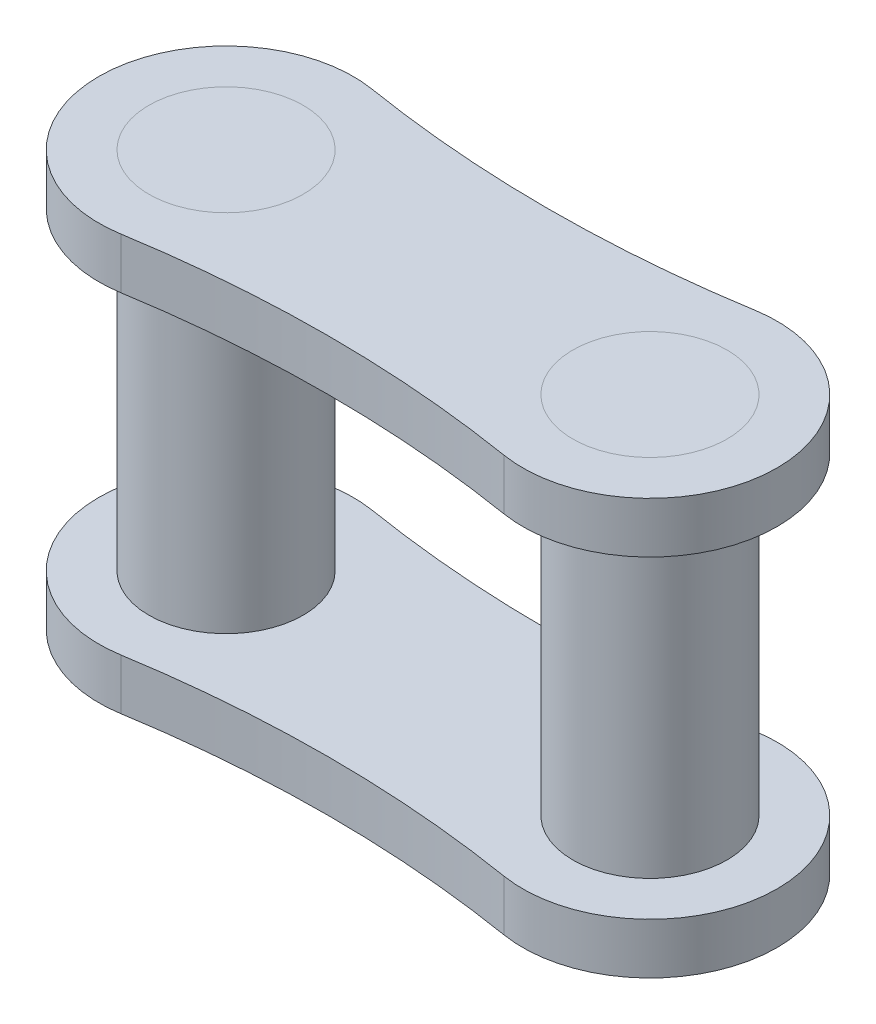
SolidWorks part; units mm, degrees
ref_plane "Front Plane" through (0, 0, 0) normal (0, 0, 1) x (1, 0, 0)
ref_plane "Top Plane" through (0, 0, 0) normal (0, 1, 0) x (1, 0, 0)
ref_plane "Right Plane" through (0, 0, 0) normal (1, 0, 0) x (0, 0, -1)
sketch "Sketch1" plane through (0, 0, 0) normal (0, 1, 0) x (1, 0, 0)
  line L0 (-3.175, 0) -> (3.175, 0) construction
  arc A0 (-2.8677, 1.8801) -> (-2.8677, -1.8801) centre (-3.175, 0) ccw
  arc A1 (2.8677, -1.8801) -> (2.8677, 1.8801) centre (3.175, 0) ccw
  arc A2 (-2.8677, 1.8801) -> (2.8677, 1.8801) centre (0, 19.4273) ccw
  arc A3 (-2.8677, -1.8801) -> (2.8677, -1.8801) centre (0, -19.4273) cw
  point P2 (0, 0)
  dimension "D2" = 3.81
  dimension "D3" = 17.78
  dimension "D1" = 6.35
extrude "Boss-Extrude1" add sketch "Sketch1" along normal blind 0.762
sketch "Sketch2" plane through (0, 0.762, 0) normal (0, 1, 0) x (1, 0, 0)
  line L0 (-3.175, 0) -> (3.175, 0) construction
  circle A0 centre (3.175, 0) radius 1.1557
  circle A1 centre (-3.175, 0) radius 1.1557
  point P2 (0, 0)
  dimension "D1" = 2.3114
  dimension "D2" = 6.35
extrude "Cut-Extrude1" cut sketch "Sketch2" against normal blind 4.699
extrude "Boss-Extrude3" add sketch "Sketch2<2>" along normal blind 4.699 and the other way blind 0.762 separate body
sketch "Sketch2<2>" plane through (0, 0.762, 0) normal (0, 1, 0) x (1, 0, 0) same geometry as "Sketch2"
sketch "Sketch3" plane through (0, 5.461, 0) normal (0, 1, 0) x (1, 0, 0)
  circle A0 centre (3.175, 0) radius 1.1557 construction
  circle A1 centre (-3.175, 0) radius 1.1557 construction
  circle A2 centre (3.175, 0) radius 1.1557
  circle A3 centre (-3.175, 0) radius 1.1557
  arc A4 (-2.8677, 1.8801) -> (2.8677, 1.8801) centre (0, 19.4273) ccw
  arc A5 (-2.8677, 1.8801) -> (-2.8677, -1.8801) centre (-3.175, 0) ccw
  arc A6 (2.8677, -1.8801) -> (-2.8677, -1.8801) centre (0, -19.4273) ccw
  arc A7 (2.8677, -1.8801) -> (2.8677, 1.8801) centre (3.175, 0) ccw
  arc A8 (-2.8677, 1.8801) -> (2.8677, 1.8801) centre (0, 19.4273) ccw
  arc A9 (-2.8677, 1.8801) -> (-2.8677, -1.8801) centre (-3.175, 0) ccw
  arc A10 (2.8677, -1.8801) -> (-2.8677, -1.8801) centre (0, -19.4273) ccw
  arc A11 (2.8677, -1.8801) -> (2.8677, 1.8801) centre (3.175, 0) ccw
  dimension "D1" = 0
extrude "Boss-Extrude4" add sketch "Sketch3" along normal blind 0.762 separate body
sketch "Sketch4" plane through (0, 5.461, 0) normal (0, 1, 0) x (1, 0, 0)
  circle A0 centre (3.175, 0) radius 1.1557 construction
  circle A1 centre (-3.175, 0) radius 1.1557 construction
  circle A2 centre (3.175, 0) radius 1.1557
  circle A3 centre (-3.175, 0) radius 1.1557
extrude "Boss-Extrude6" add sketch "Sketch4" along normal blind 0.762 separate body
ref_plane "Mid Plane" through (0, 3.1115, 0) normal (0, -1, 0) x (-1, 0, 0)
